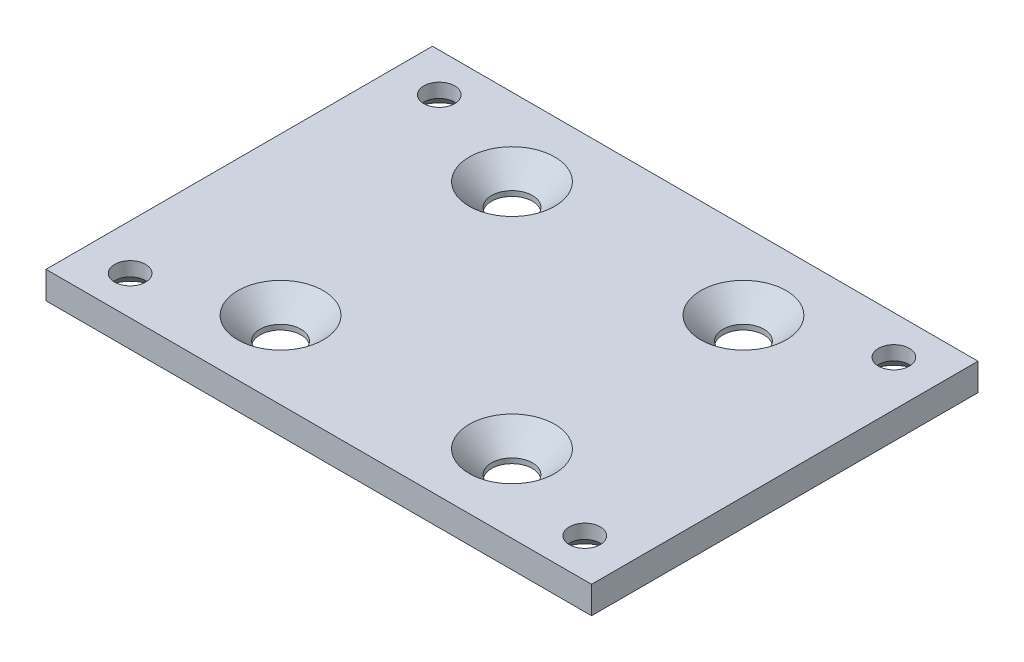
SolidWorks part; units mm, degrees
material "6061-T6 (SS)"
ref_plane "Front Plane" through (0, 0, 0) normal (0, 0, 1) x (1, 0, 0)
ref_plane "Top Plane" through (0, 0, 0) normal (0, 1, 0) x (1, 0, 0)
ref_plane "Right Plane" through (0, 0, 0) normal (1, 0, 0) x (0, 0, -1)
sketch "Base Plate" plane through (0, 0, 0) normal (0, 1, 0) x (1, 0, 0)
  line L9 (-30, -21.25) -> (30, -21.25)
  line L10 (-30, -21.25) -> (-30, 21.25)
  line L15 (-30, 21.25) -> (30, 21.25)
  line L16 (30, -21.25) -> (30, 21.25)
  line L17 (-30, -21.25) -> (30, 21.25) construction
  line L18 (-30, 21.25) -> (30, -21.25) construction
  point P0 (0, 0)
  dimension "D1" = 42.5
  dimension "D2" = 60
extrude "Boss-Extrude1" add sketch "Base Plate" along normal blind 3
hole_wizard "Motor Holes M4" positions "Sketch3" profile "Sketch4" countersink size "M4" standard "ANSI Metric" end condition through all
sketch "Sketch3" plane through (0, 3, 0) normal (0, 1, 0) x (1, 0, 0)
  line L0 (-12.7279, 12.7279) -> (0, 0) construction
  line L2 (-30, -21.25) -> (30, -21.25) construction
  circle A0 centre (0, 0) radius 18 construction
  point P5 (-12.7279, 12.7279)
  point P23 (12.7279, 12.7279)
  point P24 (12.7279, -12.7279)
  point P25 (-12.7279, -12.7279)
  dimension "D1" = 36
  dimension "D3" = 4
  dimension "D2" = 45
sketch "Sketch4" plane through (-12.7279, 3, 12.7279) normal (1, 0, 0) x (0, 0, 1)
  line L0 (0, 0) -> (0, 3)
  line L1 (0, 3) -> (2.25, 3)
  line L2 (2.25, 3) -> (2.25, 2.45)
  line L3 (2.25, 2.45) -> (4.7, 0)
  line L5 (4.7, 0) -> (0, 0)
  line L6 (-2.25, 2.45) -> (-4.7, 0) construction
  line L11 (0, -6.35) -> (0, 107.95) construction
  dimension "Thru Hole Dia." = 4.5
  dimension "Thru Hole Depth" = 3
  dimension "Near C'Sink Dia." = 9.4
  dimension "Near C'Sink Angle" = 90
hole_wizard "Clamp Holes M3" positions "Sketch5" profile "Sketch6" countersink size "M3" standard "ANSI Metric" end condition through all
sketch "Sketch5" plane through (0, 0, 0) normal (0, -1, 0) x (-1, 0, 0)
  line L1 (-25, -17) -> (25, -17)
  line L2 (-25, -17) -> (-25, 17)
  line L3 (-25, 17) -> (25, 17)
  line L4 (25, -17) -> (25, 17)
  line L5 (-25, -17) -> (25, 17) construction
  line L6 (-25, 17) -> (25, -17) construction
  point P2 (25, 17)
  point P5 (-25, -17)
  point P6 (-25, 17)
  point P7 (25, -17)
  point P191 (0, 17)
  point P193 (25, 0)
  dimension "D1" = 34
  dimension "D2" = 50
sketch "Sketch6" plane through (-25, 0, -17) normal (1, 0, 0) x (0, 0, -1)
  line L0 (0, 0) -> (0, 3)
  line L1 (0, 3) -> (1.7, 3)
  line L2 (1.7, 3) -> (1.7, 1.45)
  line L3 (1.7, 1.45) -> (3.15, 0)
  line L5 (3.15, 0) -> (0, 0)
  line L6 (-1.7, 1.45) -> (-3.15, 0) construction
  line L11 (0, -6.35) -> (0, 107.95) construction
  dimension "Thru Hole Dia." = 3.4
  dimension "Thru Hole Depth" = 3
  dimension "Near C'Sink Dia." = 6.3
  dimension "Near C'Sink Angle" = 90
